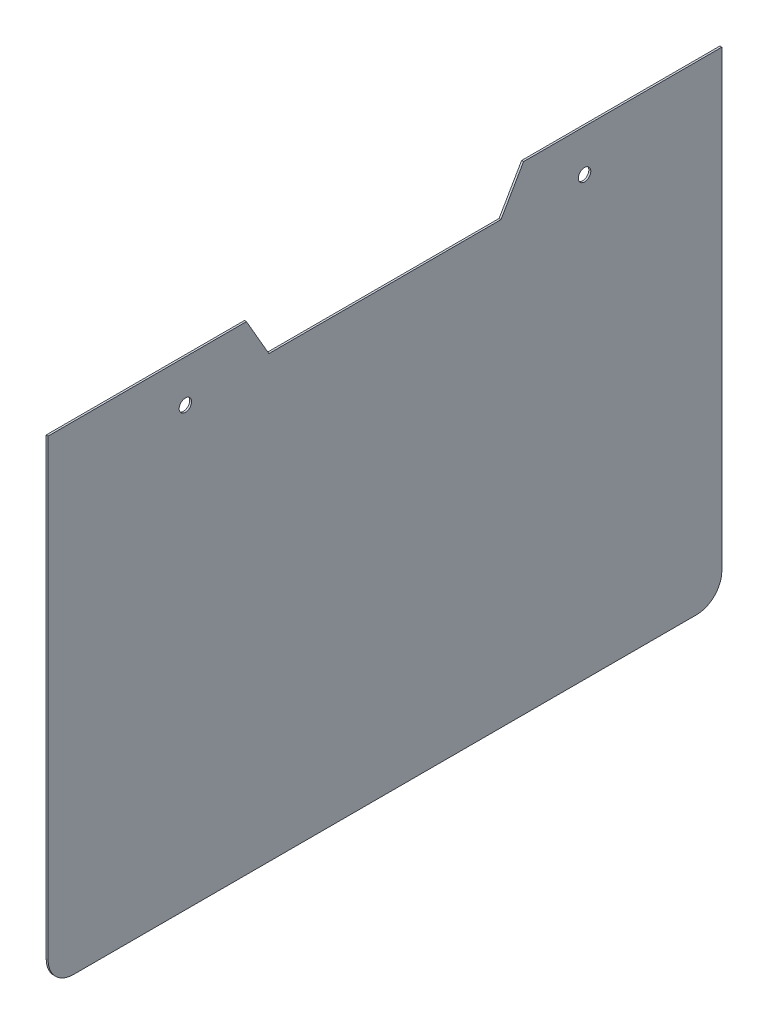
SolidWorks part; units mm, degrees
ref_plane "Front Plane" through (0, 0, 0) normal (0, 0, 1) x (1, 0, 0)
ref_plane "Top Plane" through (0, 0, 0) normal (0, 1, 0) x (1, 0, 0)
ref_plane "Right Plane" through (0, 0, 0) normal (1, 0, 0) x (0, 0, -1)
sketch "Sketch1" plane through (169.5336, 0, 0) normal (-1, 0, 0) x (0, 0, 1)
  line L0 (-82.9854, 164.2133) -> (-82.9854, 280.7133)
  line L1 (-82.9854, 280.7133) -> (-133.908, 280.7133)
  line L2 (-133.908, 280.7133) -> (-139.6815, 270.7133)
  line L3 (-139.6815, 270.7133) -> (-199.2892, 270.7133)
  line L4 (-199.2892, 270.7133) -> (-205.0627, 280.7133)
  line L5 (-205.0627, 280.7133) -> (-255.9854, 280.7133)
  line L6 (-255.9854, 280.7133) -> (-255.9854, 164.2133)
  line L7 (-249.4854, 157.7133) -> (-89.4854, 157.7133)
  line L8 (-81.9854, 164.2133) -> (-81.9854, 281.7133)
  line L9 (-81.9854, 281.7133) -> (-134.4854, 281.7133)
  line L10 (-134.4854, 281.7133) -> (-140.2589, 271.7133)
  line L11 (-140.2589, 271.7133) -> (-198.7119, 271.7133)
  line L12 (-198.7119, 271.7133) -> (-204.4854, 281.7133)
  line L13 (-204.4854, 281.7133) -> (-256.9854, 281.7133)
  line L14 (-256.9854, 281.7133) -> (-256.9854, 164.2133)
  line L15 (-249.4854, 156.7133) -> (-89.4854, 156.7133)
  line L16 (-81.9854, 164.2133) -> (-81.9854, 281.7133)
  line L17 (-81.9854, 281.7133) -> (-134.4854, 281.7133)
  line L18 (-134.4854, 281.7133) -> (-140.2589, 271.7133)
  line L19 (-140.2589, 271.7133) -> (-198.7119, 271.7133)
  line L20 (-198.7119, 271.7133) -> (-204.4854, 281.7133)
  line L21 (-204.4854, 281.7133) -> (-256.9854, 281.7133)
  line L22 (-256.9854, 281.7133) -> (-256.9854, 164.2133)
  line L23 (-249.4854, 156.7133) -> (-89.4854, 156.7133)
  arc A0 (-255.9854, 164.2133) -> (-249.4854, 157.7133) centre (-249.4854, 164.2133) ccw
  arc A1 (-89.4854, 157.7133) -> (-82.9854, 164.2133) centre (-89.4854, 164.2133) ccw
  arc A2 (-256.9854, 164.2133) -> (-249.4854, 156.7133) centre (-249.4854, 164.2133) ccw
  arc A3 (-89.4854, 156.7133) -> (-81.9854, 164.2133) centre (-89.4854, 164.2133) ccw
  arc A4 (-256.9854, 164.2133) -> (-249.4854, 156.7133) centre (-249.4854, 164.2133) ccw
  arc A5 (-89.4854, 156.7133) -> (-81.9854, 164.2133) centre (-89.4854, 164.2133) ccw
  dimension "D1" = 0
  dimension "D2" = 1
extrude "Boss-Extrude1" add sketch "Sketch1" along normal blind 0.5 contours L0 L1 L2 L3 L4 L5 L6 A0 L7 A1
sketch "Sketch2" plane through (169.0336, 0, 0) normal (-1, 0, 0) x (0, 0, 1)
  line L8 (-82.9854, 164.2133) -> (-82.9854, 280.7133)
  line L9 (-82.9854, 280.7133) -> (-133.908, 280.7133)
  line L10 (-133.908, 280.7133) -> (-139.6815, 270.7133)
  line L11 (-139.6815, 270.7133) -> (-199.2892, 270.7133)
  line L12 (-199.2892, 270.7133) -> (-205.0627, 280.7133)
  line L13 (-205.0627, 280.7133) -> (-255.9854, 280.7133)
  line L14 (-255.9854, 280.7133) -> (-255.9854, 164.2133)
  line L15 (-249.4854, 157.7133) -> (-89.4854, 157.7133)
  line L16 (-82.9854, 164.2133) -> (-82.9854, 280.7133)
  line L17 (-82.9854, 280.7133) -> (-133.908, 280.7133)
  line L18 (-133.908, 280.7133) -> (-139.6815, 270.7133)
  line L19 (-139.6815, 270.7133) -> (-199.2892, 270.7133)
  line L20 (-199.2892, 270.7133) -> (-205.0627, 280.7133)
  line L21 (-205.0627, 280.7133) -> (-255.9854, 280.7133)
  line L22 (-255.9854, 280.7133) -> (-255.9854, 164.2133)
  line L23 (-249.4854, 157.7133) -> (-89.4854, 157.7133)
  circle A0 centre (-118.2354, 269.9633) radius 1.25 construction
  circle A1 centre (-220.7354, 269.9633) radius 1.25 construction
  arc A2 (-89.4854, 157.7133) -> (-82.9854, 164.2133) centre (-89.4854, 164.2133) ccw
  arc A3 (-255.9854, 164.2133) -> (-249.4854, 157.7133) centre (-249.4854, 164.2133) ccw
  arc A4 (-89.4854, 157.7133) -> (-82.9854, 164.2133) centre (-89.4854, 164.2133) ccw
  arc A5 (-255.9854, 164.2133) -> (-249.4854, 157.7133) centre (-249.4854, 164.2133) ccw
  circle A6 centre (-118.2354, 269.9633) radius 1.25
  circle A7 centre (-220.7354, 269.9633) radius 1.25
  circle A8 centre (-220.7354, 269.9633) radius 1.6
  circle A9 centre (-118.2354, 269.9633) radius 1.6
  dimension "D2" = 3.2
  dimension "D3" = 3.2
  dimension "D1" = 0
extrude "Cut-Extrude2" cut sketch "Sketch2" against normal up to next contours A6 | A7 | A9 A6 | A8 A7 region at (169.0336, 269.9633, -118.2354) region at (169.0336, 269.9633, -220.7354) region at (169.0336, 269.9633, -222.2901) region at (169.0336, 269.9633, -119.7901)
sketch "Sketch4" plane through (169.0336, 0, -163.2571) normal (-1, 0, 0) x (0, 0, 1)
  line L0 (-13.9255, 240.4892) -> (-13.9255, 240.4522)
  line L1 (-6.3225, 222.7198) -> (-6.3055, 222.7103)
  line L2 (-6.3055, 222.7103) -> (-6.2886, 222.7198)
  line L3 (1.3145, 240.4543) -> (1.3145, 240.4913)
  line L4 (1.3145, 240.4913) -> (-13.9255, 240.4892)
  line L5 (-6.2283, 270.7133) -> (-6.2283, 157.7133) construction
  line L6 (0.7451, 239.8542) -> (0.7451, 239.8796)
  line L7 (0.7451, 239.8796) -> (-13.3752, 239.8775)
  line L8 (-13.3752, 239.8775) -> (-13.3752, 239.8521)
  line L9 (-6.3119, 223.3992) -> (-6.3003, 223.3929)
  line L10 (-6.3003, 223.3929) -> (-6.2886, 223.3992)
  line L11 (-10.4362, 235.5606) -> (-6.2367, 236.8708)
  line L12 (-6.2367, 236.8708) -> (-2.0203, 235.5606)
  line L13 (-2.0203, 235.5606) -> (-10.4362, 235.5606)
  line L14 (-4.0788, 236.2876) -> (-4.0788, 237.3714)
  line L15 (-4.0788, 237.3714) -> (-8.3534, 237.3714)
  line L16 (-8.3534, 237.3714) -> (-8.3534, 236.2982)
  line L17 (-8.3534, 236.2982) -> (-6.2367, 236.9586)
  line L18 (-6.2367, 236.9586) -> (-4.0788, 236.2876)
  line L19 (-6.7638, 238.2011) -> (-5.697, 238.2011)
  line L20 (-5.7182, 238.164) -> (-6.7289, 238.164)
  line L21 (-7.8528, 237.4094) -> (-4.5942, 237.4095)
  line L22 (-8.7672, 229.6339) -> (-8.7672, 228.3882)
  line L23 (-8.927, 228.256) -> (-9.1302, 228.2475)
  line L24 (-9.1302, 228.2475) -> (-9.1302, 228.1427)
  line L25 (-8.0602, 228.1427) -> (-8.0602, 228.2475)
  line L26 (-8.0602, 228.2475) -> (-8.2359, 228.256)
  line L27 (-8.3957, 228.3882) -> (-8.3957, 229.2942)
  line L28 (-8.3671, 230.0075) -> (-8.4021, 230.0371)
  line L29 (-9.2032, 229.5556) -> (-8.8095, 229.7376)
  line L30 (-7.2125, 229.001) -> (-7.0411, 228.9248)
  line L31 (-6.9257, 229.2571) -> (-7.0495, 229.309)
  line L32 (-5.5912, 229.6339) -> (-5.5912, 228.3882)
  line L33 (-5.751, 228.256) -> (-5.9542, 228.2475)
  line L34 (-5.9542, 228.2475) -> (-5.9542, 228.1427)
  line L35 (-4.8831, 228.1427) -> (-4.8831, 228.2475)
  line L36 (-4.8831, 228.2475) -> (-5.0588, 228.256)
  line L37 (-5.2186, 228.3882) -> (-5.2186, 229.2942)
  line L38 (-5.1911, 230.0075) -> (-5.225, 230.0371)
  line L39 (-6.0261, 229.5556) -> (-5.6335, 229.7376)
  line L40 (-4.1074, 229.6339) -> (-4.1074, 228.3882)
  line L41 (-4.2672, 228.256) -> (-4.4693, 228.2475)
  line L42 (-4.4693, 228.2475) -> (-4.4693, 228.1427)
  line L43 (-3.3994, 228.1427) -> (-3.3994, 228.2475)
  line L44 (-3.3994, 228.2475) -> (-3.5751, 228.256)
  line L45 (-3.7359, 228.3882) -> (-3.7359, 229.2942)
  line L46 (-3.7074, 230.0075) -> (-3.7413, 230.0371)
  line L47 (-4.5424, 229.5556) -> (-4.1497, 229.7376)
  line L48 (-5.697, 232.8152) -> (-5.7192, 232.8152)
  line L49 (-5.7192, 232.8152) -> (-5.7192, 232.5961)
  line L50 (-5.7192, 232.5961) -> (-5.4716, 232.5866)
  line L51 (-5.2472, 232.448) -> (-5.2472, 231.8955)
  line L52 (-4.9519, 234.0492) -> (-4.9308, 233.6873)
  line L53 (-4.9308, 233.6873) -> (-4.9297, 233.6682)
  line L54 (-4.9297, 233.6682) -> (-4.7233, 233.6682)
  line L55 (-4.7233, 233.6682) -> (-4.7138, 233.754)
  line L56 (-4.6228, 234.3424) -> (-4.6197, 234.3509)
  line L57 (-4.6197, 234.3509) -> (-4.6535, 234.4112)
  line L58 (-4.6535, 234.4112) -> (-4.6599, 234.4144)
  line L59 (-4.6048, 231.7696) -> (-4.5911, 231.7749)
  line L60 (-4.5911, 231.7749) -> (-4.5911, 232.4924)
  line L61 (-4.3879, 232.6258) -> (-4.3709, 232.629)
  line L62 (-4.3709, 232.629) -> (-4.3709, 232.8152)
  line L63 (-4.3709, 232.8152) -> (-4.3921, 232.8142)
  line L64 (-7.9513, 234.3435) -> (-7.7724, 234.3583)
  line L65 (-7.7724, 234.3583) -> (-7.7724, 234.5594)
  line L66 (-7.7724, 234.5594) -> (-7.7947, 234.5594)
  line L67 (-8.7885, 234.5583) -> (-8.8033, 234.5583)
  line L68 (-8.8033, 234.5583) -> (-8.8085, 234.5446)
  line L69 (-9.0191, 234.0588) -> (-9.7885, 232.4713)
  line L70 (-9.7885, 232.4713) -> (-10.4489, 233.8514)
  line L71 (-10.7728, 234.5446) -> (-10.7792, 234.5583)
  line L72 (-10.7792, 234.5583) -> (-10.7929, 234.5583)
  line L73 (-11.8259, 234.5583) -> (-11.8481, 234.5583)
  line L74 (-11.8481, 234.5583) -> (-11.8481, 234.3572)
  line L75 (-11.8481, 234.3572) -> (-11.6693, 234.3424)
  line L76 (-11.4819, 233.9424) -> (-11.4819, 232.1856)
  line L77 (-11.6693, 231.7855) -> (-11.8481, 231.7707)
  line L78 (-11.8481, 231.7707) -> (-11.8481, 231.5696)
  line L79 (-11.8481, 231.5696) -> (-11.8259, 231.5696)
  line L80 (-10.8405, 231.5696) -> (-10.8183, 231.5696)
  line L81 (-10.8183, 231.5696) -> (-10.8183, 231.7707)
  line L82 (-10.8183, 231.7707) -> (-10.9982, 231.7855)
  line L83 (-11.1855, 232.1856) -> (-11.1855, 233.8884)
  line L84 (-11.1855, 233.8884) -> (-10.2362, 231.9104)
  line L85 (-10.2362, 231.9104) -> (-10.2193, 231.8744)
  line L86 (-10.0827, 231.5548) -> (-10.0775, 231.541)
  line L87 (-10.0775, 231.541) -> (-9.9007, 231.541)
  line L88 (-9.9007, 231.541) -> (-9.8954, 231.5548)
  line L89 (-9.6383, 232.1231) -> (-8.7916, 233.8852)
  line L90 (-8.7916, 233.8852) -> (-8.7916, 232.1876)
  line L91 (-8.9779, 231.8014) -> (-9.1567, 231.7866)
  line L92 (-9.1567, 231.7866) -> (-9.1567, 231.5728)
  line L93 (-9.1567, 231.5728) -> (-9.0191, 231.5759)
  line L94 (-7.9142, 231.5759) -> (-7.7734, 231.5728)
  line L95 (-7.7734, 231.5728) -> (-7.7734, 231.7866)
  line L96 (-7.7734, 231.7866) -> (-7.9533, 231.8014)
  line L97 (-8.1407, 232.1887) -> (-8.1407, 233.9456)
  line L98 (-0.9557, 234.3308) -> (-0.7747, 234.3456)
  line L99 (-0.7747, 234.3456) -> (-0.7747, 234.5583)
  line L100 (-0.7747, 234.5583) -> (-0.7969, 234.5583)
  line L101 (-2.1484, 234.5583) -> (-2.1707, 234.5583)
  line L102 (-2.1707, 234.5583) -> (-2.1707, 234.3456)
  line L103 (-2.1707, 234.3456) -> (-1.9907, 234.3308)
  line L104 (-1.8023, 233.9424) -> (-1.8023, 233.282)
  line L105 (-2.1325, 233.2746) -> (-2.7686, 233.2746)
  line L106 (-3.0988, 233.282) -> (-3.0988, 233.9424)
  line L107 (-2.9093, 234.3308) -> (-2.7294, 234.3456)
  line L108 (-2.7294, 234.3456) -> (-2.7294, 234.5583)
  line L109 (-2.7294, 234.5583) -> (-2.7517, 234.5583)
  line L110 (-4.1021, 234.5583) -> (-4.1243, 234.5583)
  line L111 (-4.1243, 234.5583) -> (-4.1243, 234.3456)
  line L112 (-4.1243, 234.3456) -> (-3.9434, 234.3308)
  line L113 (-3.7561, 233.9434) -> (-3.7561, 232.1866)
  line L114 (-3.9445, 231.7971) -> (-4.1254, 231.7833)
  line L115 (-4.1254, 231.7833) -> (-4.1254, 231.5685)
  line L116 (-4.1254, 231.5685) -> (-4.0281, 231.5716)
  line L117 (-2.8311, 231.5716) -> (-2.7305, 231.5685)
  line L118 (-2.7305, 231.5685) -> (-2.7305, 231.7833)
  line L119 (-2.7305, 231.7833) -> (-2.9104, 231.7971)
  line L120 (-3.0999, 232.1866) -> (-3.0999, 232.9846)
  line L121 (-2.7697, 232.992) -> (-2.1336, 232.992)
  line L122 (-1.8034, 232.9846) -> (-1.8034, 232.1866)
  line L123 (-1.9928, 231.7971) -> (-2.1727, 231.7833)
  line L124 (-2.1727, 231.7833) -> (-2.1727, 231.5685)
  line L125 (-2.1727, 231.5685) -> (-2.0743, 231.5716)
  line L126 (-0.8763, 231.5716) -> (-0.7768, 231.5685)
  line L127 (-0.7768, 231.5685) -> (-0.7768, 231.7833)
  line L128 (-0.7768, 231.7833) -> (-0.9577, 231.7971)
  line L129 (-1.1461, 232.1855) -> (-1.1461, 233.9424)
  line L131 (-86.2283, 157.7133) -> (73.7717, 157.7133) construction
  line L133 (-6.3055, 240.4903) -> (-6.3055, 222.7103) construction
  line L134 (23.5756, 270.7133) -> (-36.0321, 270.7133) construction
  spline S0 degree 3 poles (-13.9255, 240.4522) (-13.9255, 232.1824) (-13.9255, 226.7203) (-6.3225, 222.7198) knots 0.125 0.125 0.125 0.125 0.25 0.25 0.25 0.25
  spline S1 degree 3 poles (-6.2886, 222.7198) (1.3145, 226.7034) (1.3145, 232.1739) (1.3145, 240.4543) knots 0.5 0.5 0.5 0.5 0.625 0.625 0.625 0.625
  spline S4 degree 3 poles (-13.3752, 239.8521) (-13.3752, 239.6256) (-13.3752, 239.3991) (-13.3763, 239.1737) knots 0.25 0.25 0.25 0.25 0.333333 0.333333 0.333333 0.333333
  spline S5 degree 3 poles (-13.3763, 239.1737) (-13.3815, 236.0336) (-13.3858, 233.0682) (-12.5042, 230.3493) knots 0.333333 0.333333 0.333333 0.333333 0.416667 0.416667 0.416667 0.416667
  spline S6 degree 3 poles (-12.5042, 230.3493) (-12.0301, 228.8867) (-11.3432, 227.64) (-10.4045, 226.5372) knots 0.416667 0.416667 0.416667 0.416667 0.5 0.5 0.5 0.5
  spline S7 degree 3 poles (-10.4045, 226.5372) (-9.3535, 225.3021) (-8.0147, 224.2756) (-6.3119, 223.3992) knots 0.5 0.5 0.5 0.5 0.583333 0.583333 0.583333 0.583333
  spline S8 degree 3 poles (-6.2886, 223.3992) (0.7588, 227.06) (0.7525, 232.9888) (0.7451, 239.2636) knots 0.75 0.75 0.75 0.75 0.833333 0.833333 0.833333 0.833333
  spline S9 degree 3 poles (0.7451, 239.2636) (0.7451, 239.4605) (0.7451, 239.6574) (0.7451, 239.8542) knots 0.833333 0.833333 0.833333 0.833333 1 1 1 1
  spline S10 degree 3 poles (-5.697, 238.2011) (-5.6917, 238.5673) (-5.9859, 238.8467) (-6.2378, 239.07) knots 0.25 0.25 0.25 0.25 0.5 0.5 0.5 0.5
  spline S11 degree 3 poles (-6.2378, 239.07) (-6.4865, 238.8424) (-6.7638, 238.5779) (-6.7638, 238.2011) knots 0.5 0.5 0.5 0.5 1 1 1 1
  spline S12 degree 3 poles (-6.7289, 238.164) (-7.239, 238.0497) (-7.6539, 237.7714) (-7.8528, 237.4094) knots 0.2 0.2 0.2 0.2 0.4 0.4 0.4 0.4
  spline S13 degree 3 poles (-4.5942, 237.4095) (-4.7932, 237.7714) (-5.2081, 238.0508) (-5.7182, 238.164) knots 0.6 0.6 0.6 0.6 1 1 1 1
  spline S14 degree 3 poles (-8.8095, 229.7376) (-8.7651, 229.7577) (-8.7672, 229.6932) (-8.7672, 229.6339) knots 0 0 0 0 0.058824 0.058824 0.058824 0.058824
  spline S15 degree 3 poles (-8.7672, 228.3882) (-8.7672, 228.293) (-8.8371, 228.2612) (-8.927, 228.256) knots 0.117647 0.117647 0.117647 0.117647 0.176471 0.176471 0.176471 0.176471
  spline S16 degree 3 poles (-9.1302, 228.1427) (-8.8011, 228.1459) (-8.6794, 228.1512) (-8.5587, 228.1512) knots 0.294118 0.294118 0.294118 0.294118 0.352941 0.352941 0.352941 0.352941
  spline S17 degree 3 poles (-8.5587, 228.1512) (-8.4349, 228.1512) (-8.3163, 228.1459) (-8.0602, 228.1427) knots 0.352941 0.352941 0.352941 0.352941 0.411765 0.411765 0.411765 0.411765
  spline S18 degree 3 poles (-8.2359, 228.256) (-8.3248, 228.2612) (-8.3957, 228.292) (-8.3957, 228.3882) knots 0.529412 0.529412 0.529412 0.529412 0.588235 0.588235 0.588235 0.588235
  spline S19 degree 3 poles (-8.3957, 229.2942) (-8.3957, 229.6307) (-8.3767, 229.872) (-8.3671, 230.0075) knots 0.647059 0.647059 0.647059 0.647059 0.705882 0.705882 0.705882 0.705882
  spline S20 degree 3 poles (-8.4021, 230.0371) (-8.6444, 229.9408) (-9.0371, 229.8011) (-9.2424, 229.7524) knots 0.764706 0.764706 0.764706 0.764706 0.823529 0.823529 0.823529 0.823529
  spline S21 degree 3 poles (-9.2424, 229.7524) (-9.2466, 229.6932) (-9.2339, 229.6307) (-9.2032, 229.5556) knots 0.823529 0.823529 0.823529 0.823529 0.882353 0.882353 0.882353 0.882353
  spline S22 degree 3 poles (-7.0411, 228.9248) (-6.8813, 228.8539) (-6.7479, 228.766) (-6.7479, 228.5692) knots 0 0 0 0 0.166667 0.166667 0.166667 0.166667
  spline S23 degree 3 poles (-6.7479, 228.5692) (-6.7479, 228.3978) (-6.8718, 228.2485) (-7.0496, 228.2485) knots 0.166667 0.166667 0.166667 0.166667 0.333333 0.333333 0.333333 0.333333
  spline S24 degree 3 poles (-7.0496, 228.2485) (-7.2602, 228.2485) (-7.4062, 228.4178) (-7.4062, 228.6232) knots 0.333333 0.333333 0.333333 0.333333 0.5 0.5 0.5 0.5
  spline S25 degree 3 poles (-7.4062, 228.6232) (-7.4062, 228.7957) (-7.3385, 228.8941) (-7.2125, 229.001) knots 0.5 0.5 0.5 0.5 0.666667 0.666667 0.666667 0.666667
  spline S26 degree 3 poles (-7.0495, 229.309) (-7.1818, 229.3661) (-7.3194, 229.4423) (-7.3194, 229.6116) knots 0 0 0 0 0.166667 0.166667 0.166667 0.166667
  spline S27 degree 3 poles (-7.3194, 229.6116) (-7.3194, 229.7714) (-7.2041, 229.8614) (-7.0495, 229.8614) knots 0.166667 0.166667 0.166667 0.166667 0.333333 0.333333 0.333333 0.333333
  spline S28 degree 3 poles (-7.0495, 229.8614) (-6.8665, 229.8614) (-6.7595, 229.7323) (-6.7595, 229.5556) knots 0.333333 0.333333 0.333333 0.333333 0.5 0.5 0.5 0.5
  spline S29 degree 3 poles (-6.7595, 229.5556) (-6.7595, 229.4423) (-6.8167, 229.3439) (-6.9257, 229.2571) knots 0.5 0.5 0.5 0.5 0.666667 0.666667 0.666667 0.666667
  spline S30 degree 3 poles (-7.0136, 230.0075) (-7.3956, 230.0075) (-7.6094, 229.7948) (-7.6094, 229.4847) knots 0 0 0 0 0.111111 0.111111 0.111111 0.111111
  spline S31 degree 3 poles (-7.6094, 229.4847) (-7.6094, 229.2825) (-7.5036, 229.1439) (-7.329, 229.0518) knots 0.111111 0.111111 0.111111 0.111111 0.222222 0.222222 0.222222 0.222222
  spline S32 degree 3 poles (-7.329, 229.0518) (-7.5089, 228.9725) (-7.6581, 228.801) (-7.6581, 228.5957) knots 0.222222 0.222222 0.222222 0.222222 0.333333 0.333333 0.333333 0.333333
  spline S33 degree 3 poles (-7.6581, 228.5957) (-7.6581, 228.3544) (-7.4867, 228.1036) (-7.0919, 228.1036) knots 0.333333 0.333333 0.333333 0.333333 0.444444 0.444444 0.444444 0.444444
  spline S34 degree 3 poles (-7.0919, 228.1036) (-6.7321, 228.1036) (-6.4389, 228.3565) (-6.4389, 228.7248) knots 0.444444 0.444444 0.444444 0.444444 0.555556 0.555556 0.555556 0.555556
  spline S35 degree 3 poles (-6.4389, 228.7248) (-6.4389, 229.0116) (-6.6369, 229.1545) (-6.7882, 229.2095) knots 0.555556 0.555556 0.555556 0.555556 0.666667 0.666667 0.666667 0.666667
  spline S36 degree 3 poles (-6.7882, 229.2095) (-6.6305, 229.3101) (-6.5236, 229.435) (-6.5236, 229.5948) knots 0.666667 0.666667 0.666667 0.666667 0.777778 0.777778 0.777778 0.777778
  spline S37 degree 3 poles (-6.5236, 229.5948) (-6.5235, 229.8815) (-6.7532, 230.0075) (-7.0136, 230.0075) knots 0.777778 0.777778 0.777778 0.777778 1 1 1 1
  spline S38 degree 3 poles (-5.6335, 229.7376) (-5.5891, 229.7577) (-5.5912, 229.6932) (-5.5912, 229.6339) knots 0 0 0 0 0.058824 0.058824 0.058824 0.058824
  spline S39 degree 3 poles (-5.5912, 228.3882) (-5.5912, 228.293) (-5.661, 228.2612) (-5.751, 228.256) knots 0.117647 0.117647 0.117647 0.117647 0.176471 0.176471 0.176471 0.176471
  spline S40 degree 3 poles (-5.9542, 228.1427) (-5.625, 228.1459) (-5.5033, 228.1512) (-5.3827, 228.1512) knots 0.294118 0.294118 0.294118 0.294118 0.352941 0.352941 0.352941 0.352941
  spline S41 degree 3 poles (-5.3827, 228.1512) (-5.2588, 228.1512) (-5.1403, 228.1459) (-4.8831, 228.1427) knots 0.352941 0.352941 0.352941 0.352941 0.411765 0.411765 0.411765 0.411765
  spline S42 degree 3 poles (-5.0588, 228.256) (-5.1488, 228.2612) (-5.2186, 228.292) (-5.2186, 228.3882) knots 0.529412 0.529412 0.529412 0.529412 0.588235 0.588235 0.588235 0.588235
  spline S43 degree 3 poles (-5.2186, 229.2942) (-5.2186, 229.6307) (-5.1996, 229.872) (-5.1911, 230.0075) knots 0.647059 0.647059 0.647059 0.647059 0.705882 0.705882 0.705882 0.705882
  spline S44 degree 3 poles (-5.225, 230.0371) (-5.4663, 229.9408) (-5.86, 229.8011) (-6.0663, 229.7524) knots 0.764706 0.764706 0.764706 0.764706 0.823529 0.823529 0.823529 0.823529
  spline S45 degree 3 poles (-6.0663, 229.7524) (-6.0685, 229.6932) (-6.0579, 229.6307) (-6.0261, 229.5556) knots 0.823529 0.823529 0.823529 0.823529 0.882353 0.882353 0.882353 0.882353
  spline S46 degree 3 poles (-4.1497, 229.7376) (-4.1053, 229.7577) (-4.1074, 229.6932) (-4.1074, 229.6339) knots 0 0 0 0 0.058824 0.058824 0.058824 0.058824
  spline S47 degree 3 poles (-4.1074, 228.3882) (-4.1074, 228.293) (-4.1772, 228.2612) (-4.2672, 228.256) knots 0.117647 0.117647 0.117647 0.117647 0.176471 0.176471 0.176471 0.176471
  spline S48 degree 3 poles (-4.4693, 228.1427) (-4.1402, 228.1459) (-4.0185, 228.1512) (-3.8989, 228.1512) knots 0.294118 0.294118 0.294118 0.294118 0.352941 0.352941 0.352941 0.352941
  spline S49 degree 3 poles (-3.8989, 228.1512) (-3.7751, 228.1512) (-3.6565, 228.1459) (-3.3994, 228.1427) knots 0.352941 0.352941 0.352941 0.352941 0.411765 0.411765 0.411765 0.411765
  spline S50 degree 3 poles (-3.5751, 228.256) (-3.665, 228.2612) (-3.7359, 228.292) (-3.7359, 228.3882) knots 0.529412 0.529412 0.529412 0.529412 0.588235 0.588235 0.588235 0.588235
  spline S51 degree 3 poles (-3.7359, 229.2942) (-3.7359, 229.6307) (-3.7169, 229.872) (-3.7074, 230.0075) knots 0.647059 0.647059 0.647059 0.647059 0.705882 0.705882 0.705882 0.705882
  spline S52 degree 3 poles (-3.7413, 230.0371) (-3.9826, 229.9408) (-4.3763, 229.8011) (-4.5826, 229.7524) knots 0.764706 0.764706 0.764706 0.764706 0.823529 0.823529 0.823529 0.823529
  spline S53 degree 3 poles (-4.5826, 229.7524) (-4.5858, 229.6932) (-4.5741, 229.6307) (-4.5424, 229.5556) knots 0.823529 0.823529 0.823529 0.823529 0.882353 0.882353 0.882353 0.882353
  spline S54 degree 3 poles (-4.3921, 232.8142) (-4.4524, 232.8131) (-4.5159, 232.811) (-4.5815, 232.8099) knots 0 0 0 0 0.03125 0.03125 0.03125 0.03125
  spline S55 degree 3 poles (-4.5815, 232.8099) (-4.7445, 232.8057) (-4.9149, 232.8014) (-5.0651, 232.8014) knots 0.03125 0.03125 0.03125 0.03125 0.0625 0.0625 0.0625 0.0625
  spline S56 degree 3 poles (-5.0651, 232.8014) (-5.1943, 232.8014) (-5.3265, 232.8046) (-5.4546, 232.8088) knots 0.0625 0.0625 0.0625 0.0625 0.09375 0.09375 0.09375 0.09375
  spline S57 degree 3 poles (-5.4546, 232.8088) (-5.5351, 232.811) (-5.6165, 232.8131) (-5.697, 232.8152) knots 0.09375 0.09375 0.09375 0.09375 0.125 0.125 0.125 0.125
  spline S58 degree 3 poles (-5.4716, 232.5866) (-5.3255, 232.5813) (-5.2472, 232.557) (-5.2472, 232.448) knots 0.21875 0.21875 0.21875 0.21875 0.25 0.25 0.25 0.25
  spline S59 degree 3 poles (-5.2472, 231.8955) (-5.4324, 231.8267) (-5.5997, 231.7939) (-5.7721, 231.7939) knots 0.28125 0.28125 0.28125 0.28125 0.3125 0.3125 0.3125 0.3125
  spline S60 degree 3 poles (-5.7721, 231.7939) (-6.6103, 231.7939) (-6.9077, 232.5337) (-6.9077, 233.1676) knots 0.3125 0.3125 0.3125 0.3125 0.34375 0.34375 0.34375 0.34375
  spline S61 degree 3 poles (-6.9077, 233.1676) (-6.9077, 233.8873) (-6.4971, 234.3339) (-5.8357, 234.3339) knots 0.34375 0.34375 0.34375 0.34375 0.375 0.375 0.375 0.375
  spline S62 degree 3 poles (-5.8357, 234.3339) (-5.4494, 234.3339) (-5.1043, 234.2228) (-4.9519, 234.0492) knots 0.375 0.375 0.375 0.375 0.40625 0.40625 0.40625 0.40625
  spline S63 degree 3 poles (-4.7138, 233.754) (-4.6916, 233.9445) (-4.6599, 234.2059) (-4.6228, 234.3424) knots 0.53125 0.53125 0.53125 0.53125 0.5625 0.5625 0.5625 0.5625
  spline S64 degree 3 poles (-4.6599, 234.4144) (-5.097, 234.5943) (-5.5076, 234.6186) (-5.8516, 234.6186) knots 0.65625 0.65625 0.65625 0.65625 0.6875 0.6875 0.6875 0.6875
  spline S65 degree 3 poles (-5.8516, 234.6186) (-6.7194, 234.6186) (-7.5957, 234.1529) (-7.5957, 233.1126) knots 0.6875 0.6875 0.6875 0.6875 0.71875 0.71875 0.71875 0.71875
  spline S66 degree 3 poles (-7.5957, 233.1126) (-7.5957, 232.1252) (-6.9343, 231.5114) (-5.8695, 231.5114) knots 0.71875 0.71875 0.71875 0.71875 0.75 0.75 0.75 0.75
  spline S67 degree 3 poles (-5.8695, 231.5114) (-5.4674, 231.5114) (-5.0536, 231.596) (-4.6048, 231.7696) knots 0.75 0.75 0.75 0.75 0.78125 0.78125 0.78125 0.78125
  spline S68 degree 3 poles (-4.5911, 232.4924) (-4.5911, 232.5803) (-4.5392, 232.5951) (-4.3879, 232.6258) knots 0.84375 0.84375 0.84375 0.84375 0.875 0.875 0.875 0.875
  spline S69 degree 3 poles (-8.1111, 234.2821) (-8.0952, 234.3138) (-8.0634, 234.3339) (-7.9513, 234.3435) knots 0 0 0 0 0.015152 0.015152 0.015152 0.015152
  spline S70 degree 3 poles (-7.7947, 234.5594) (-7.8846, 234.5572) (-7.964, 234.5551) (-8.036, 234.552) knots 0.060606 0.060606 0.060606 0.060606 0.075758 0.075758 0.075758 0.075758
  spline S71 degree 3 poles (-8.036, 234.552) (-8.1344, 234.5488) (-8.2201, 234.5456) (-8.2942, 234.5456) knots 0.075758 0.075758 0.075758 0.075758 0.090909 0.090909 0.090909 0.090909
  spline S72 degree 3 poles (-8.2942, 234.5456) (-8.3673, 234.5456) (-8.454, 234.5488) (-8.5535, 234.552) knots 0.090909 0.090909 0.090909 0.090909 0.106061 0.106061 0.106061 0.106061
  spline S73 degree 3 poles (-8.5535, 234.552) (-8.6244, 234.5541) (-8.7017, 234.5572) (-8.7885, 234.5583) knots 0.106061 0.106061 0.106061 0.106061 0.121212 0.121212 0.121212 0.121212
  spline S74 degree 3 poles (-8.8085, 234.5446) (-8.8276, 234.5012) (-8.8467, 234.4556) (-8.8657, 234.408) knots 0.151515 0.151515 0.151515 0.151515 0.166667 0.166667 0.166667 0.166667
  spline S75 degree 3 poles (-8.8657, 234.408) (-8.9144, 234.2916) (-8.9641, 234.171) (-9.0191, 234.0588) knots 0.166667 0.166667 0.166667 0.166667 0.181818 0.181818 0.181818 0.181818
  spline S76 degree 3 poles (-10.4489, 233.8514) (-10.4796, 233.917) (-10.5167, 233.9964) (-10.5569, 234.08) knots 0.212121 0.212121 0.212121 0.212121 0.227273 0.227273 0.227273 0.227273
  spline S77 degree 3 poles (-10.5569, 234.08) (-10.6341, 234.243) (-10.7209, 234.4282) (-10.7728, 234.5446) knots 0.227273 0.227273 0.227273 0.227273 0.242424 0.242424 0.242424 0.242424
  spline S78 degree 3 poles (-10.7929, 234.5583) (-10.8406, 234.5573) (-10.8882, 234.5552) (-10.9369, 234.5541) knots 0.272727 0.272727 0.272727 0.272727 0.287879 0.287879 0.287879 0.287879
  spline S79 degree 3 poles (-10.9369, 234.5541) (-11.1792, 234.5456) (-11.4353, 234.5446) (-11.6809, 234.5541) knots 0.287879 0.287879 0.287879 0.287879 0.30303 0.30303 0.30303 0.30303
  spline S80 degree 3 poles (-11.6809, 234.5541) (-11.7295, 234.5551) (-11.7772, 234.5572) (-11.8259, 234.5583) knots 0.30303 0.30303 0.30303 0.30303 0.318182 0.318182 0.318182 0.318182
  spline S81 degree 3 poles (-11.6693, 234.3424) (-11.5581, 234.334) (-11.5264, 234.3128) (-11.5095, 234.2821) knots 0.363636 0.363636 0.363636 0.363636 0.378788 0.378788 0.378788 0.378788
  spline S82 degree 3 poles (-11.5095, 234.2821) (-11.4872, 234.2334) (-11.4819, 234.1212) (-11.4819, 233.9424) knots 0.378788 0.378788 0.378788 0.378788 0.393939 0.393939 0.393939 0.393939
  spline S83 degree 3 poles (-11.4819, 232.1856) (-11.4819, 232.0109) (-11.4862, 231.8934) (-11.5095, 231.848) knots 0.409091 0.409091 0.409091 0.409091 0.424242 0.424242 0.424242 0.424242
  spline S84 degree 3 poles (-11.5095, 231.848) (-11.5264, 231.8152) (-11.5581, 231.794) (-11.6693, 231.7855) knots 0.424242 0.424242 0.424242 0.424242 0.439394 0.439394 0.439394 0.439394
  spline S85 degree 3 poles (-11.8259, 231.5696) (-11.774, 231.5707) (-11.7211, 231.5728) (-11.6682, 231.5749) knots 0.484848 0.484848 0.484848 0.484848 0.5 0.5 0.5 0.5
  spline S86 degree 3 poles (-11.6682, 231.5749) (-11.5571, 231.5792) (-11.4427, 231.5834) (-11.3316, 231.5834) knots 0.5 0.5 0.5 0.5 0.515152 0.515152 0.515152 0.515152
  spline S87 degree 3 poles (-11.3316, 231.5834) (-11.2205, 231.5834) (-11.1083, 231.5792) (-10.9993, 231.5749) knots 0.515152 0.515152 0.515152 0.515152 0.530303 0.530303 0.530303 0.530303
  spline S88 degree 3 poles (-10.9993, 231.5749) (-10.9464, 231.5728) (-10.8935, 231.5707) (-10.8405, 231.5696) knots 0.530303 0.530303 0.530303 0.530303 0.545455 0.545455 0.545455 0.545455
  spline S89 degree 3 poles (-10.9982, 231.7855) (-11.1083, 231.794) (-11.1411, 231.8152) (-11.158, 231.8469) knots 0.590909 0.590909 0.590909 0.590909 0.606061 0.606061 0.606061 0.606061
  spline S90 degree 3 poles (-11.158, 231.8469) (-11.1813, 231.8935) (-11.1855, 232.011) (-11.1855, 232.1856) knots 0.606061 0.606061 0.606061 0.606061 0.621212 0.621212 0.621212 0.621212
  spline S91 degree 3 poles (-10.2193, 231.8744) (-10.1685, 231.7654) (-10.1208, 231.6627) (-10.0827, 231.5548) knots 0.666667 0.666667 0.666667 0.666667 0.681818 0.681818 0.681818 0.681818
  spline S92 degree 3 poles (-9.8954, 231.5548) (-9.8383, 231.6987) (-9.7536, 231.885) (-9.6383, 232.1231) knots 0.727273 0.727273 0.727273 0.727273 0.742424 0.742424 0.742424 0.742424
  spline S93 degree 3 poles (-8.7916, 232.1876) (-8.7916, 232.013) (-8.7958, 231.8955) (-8.8191, 231.85) knots 0.772727 0.772727 0.772727 0.772727 0.787879 0.787879 0.787879 0.787879
  spline S94 degree 3 poles (-8.8191, 231.85) (-8.8329, 231.8225) (-8.8794, 231.8077) (-8.9779, 231.8014) knots 0.787879 0.787879 0.787879 0.787879 0.80303 0.80303 0.80303 0.80303
  spline S95 degree 3 poles (-9.0191, 231.5759) (-8.8625, 231.5802) (-8.6688, 231.5854) (-8.4635, 231.5854) knots 0.848485 0.848485 0.848485 0.848485 0.863636 0.863636 0.863636 0.863636
  spline S96 degree 3 poles (-8.4635, 231.5854) (-8.2634, 231.5854) (-8.0697, 231.5802) (-7.9142, 231.5759) knots 0.863636 0.863636 0.863636 0.863636 0.878788 0.878788 0.878788 0.878788
  spline S97 degree 3 poles (-7.9533, 231.8014) (-8.0518, 231.8088) (-8.0983, 231.8236) (-8.1131, 231.85) knots 0.924242 0.924242 0.924242 0.924242 0.939394 0.939394 0.939394 0.939394
  spline S98 degree 3 poles (-8.1131, 231.85) (-8.1364, 231.8966) (-8.1407, 232.0141) (-8.1407, 232.1887) knots 0.939394 0.939394 0.939394 0.939394 0.954545 0.954545 0.954545 0.954545
  spline S99 degree 3 poles (-8.1407, 233.9456) (-8.1386, 234.1212) (-8.1343, 234.2345) (-8.1111, 234.2821) knots 0.969697 0.969697 0.969697 0.969697 1 1 1 1
  spline S100 degree 3 poles (-1.1155, 234.2821) (-1.1017, 234.3085) (-1.0541, 234.3234) (-0.9557, 234.3308) knots 0 0 0 0 0.015385 0.015385 0.015385 0.015385
  spline S101 degree 3 poles (-0.7969, 234.5583) (-0.8456, 234.5572) (-0.8985, 234.5562) (-0.9557, 234.5551) knots 0.061538 0.061538 0.061538 0.061538 0.076923 0.076923 0.076923 0.076923
  spline S102 degree 3 poles (-0.9557, 234.5551) (-1.1091, 234.5509) (-1.2849, 234.5466) (-1.4711, 234.5466) knots 0.076923 0.076923 0.076923 0.076923 0.092308 0.092308 0.092308 0.092308
  spline S103 degree 3 poles (-1.4711, 234.5466) (-1.6605, 234.5466) (-1.8352, 234.5509) (-1.9907, 234.5551) knots 0.092308 0.092308 0.092308 0.092308 0.107692 0.107692 0.107692 0.107692
  spline S104 degree 3 poles (-1.9907, 234.5551) (-2.0479, 234.5562) (-2.1008, 234.5583) (-2.1484, 234.5583) knots 0.107692 0.107692 0.107692 0.107692 0.123077 0.123077 0.123077 0.123077
  spline S105 degree 3 poles (-1.9907, 234.3308) (-1.8913, 234.3234) (-1.8436, 234.3085) (-1.8299, 234.2821) knots 0.169231 0.169231 0.169231 0.169231 0.184615 0.184615 0.184615 0.184615
  spline S106 degree 3 poles (-1.8299, 234.2821) (-1.8045, 234.2313) (-1.8023, 234.0926) (-1.8023, 233.9424) knots 0.184615 0.184615 0.184615 0.184615 0.2 0.2 0.2 0.2
  spline S107 degree 3 poles (-1.8023, 233.282) (-1.8648, 233.2788) (-1.9495, 233.2746) (-2.1325, 233.2746) knots 0.215385 0.215385 0.215385 0.215385 0.230769 0.230769 0.230769 0.230769
  spline S108 degree 3 poles (-2.7686, 233.2746) (-2.9517, 233.2746) (-3.0363, 233.2788) (-3.0988, 233.282) knots 0.246154 0.246154 0.246154 0.246154 0.261538 0.261538 0.261538 0.261538
  spline S109 degree 3 poles (-3.0988, 233.9424) (-3.0988, 234.099) (-3.0967, 234.2324) (-3.0713, 234.2821) knots 0.276923 0.276923 0.276923 0.276923 0.292308 0.292308 0.292308 0.292308
  spline S110 degree 3 poles (-3.0713, 234.2821) (-3.0575, 234.3085) (-3.0099, 234.3234) (-2.9093, 234.3308) knots 0.292308 0.292308 0.292308 0.292308 0.307692 0.307692 0.307692 0.307692
  spline S111 degree 3 poles (-2.7517, 234.5583) (-2.8003, 234.5572) (-2.8543, 234.5562) (-2.9115, 234.5551) knots 0.353846 0.353846 0.353846 0.353846 0.369231 0.369231 0.369231 0.369231
  spline S112 degree 3 poles (-2.9115, 234.5551) (-3.0649, 234.5509) (-3.2395, 234.5466) (-3.4237, 234.5466) knots 0.369231 0.369231 0.369231 0.369231 0.384615 0.384615 0.384615 0.384615
  spline S113 degree 3 poles (-3.4237, 234.5466) (-3.6131, 234.5466) (-3.7899, 234.5509) (-3.9444, 234.5551) knots 0.384615 0.384615 0.384615 0.384615 0.4 0.4 0.4 0.4
  spline S114 degree 3 poles (-3.9444, 234.5551) (-4.0005, 234.5562) (-4.0534, 234.5583) (-4.1021, 234.5583) knots 0.4 0.4 0.4 0.4 0.415385 0.415385 0.415385 0.415385
  spline S115 degree 3 poles (-3.9434, 234.3308) (-3.8449, 234.3234) (-3.7963, 234.3085) (-3.7836, 234.2821) knots 0.461538 0.461538 0.461538 0.461538 0.476923 0.476923 0.476923 0.476923
  spline S116 degree 3 poles (-3.7836, 234.2821) (-3.7582, 234.2334) (-3.7561, 234.099) (-3.7561, 233.9434) knots 0.476923 0.476923 0.476923 0.476923 0.492308 0.492308 0.492308 0.492308
  spline S117 degree 3 poles (-3.7561, 232.1866) (-3.7561, 232.0299) (-3.7582, 231.8976) (-3.7836, 231.8468) knots 0.507692 0.507692 0.507692 0.507692 0.523077 0.523077 0.523077 0.523077
  spline S118 degree 3 poles (-3.7836, 231.8468) (-3.7973, 231.8193) (-3.8429, 231.8056) (-3.9445, 231.7971) knots 0.523077 0.523077 0.523077 0.523077 0.538462 0.538462 0.538462 0.538462
  spline S119 degree 3 poles (-4.0281, 231.5716) (-3.8598, 231.5759) (-3.6513, 231.5822) (-3.4259, 231.5822) knots 0.584615 0.584615 0.584615 0.584615 0.6 0.6 0.6 0.6
  spline S120 degree 3 poles (-3.4259, 231.5822) (-3.2068, 231.5822) (-2.9983, 231.5759) (-2.8311, 231.5716) knots 0.6 0.6 0.6 0.6 0.615385 0.615385 0.615385 0.615385
  spline S121 degree 3 poles (-2.9104, 231.7971) (-3.012, 231.8056) (-3.0586, 231.8193) (-3.0723, 231.8468) knots 0.661538 0.661538 0.661538 0.661538 0.676923 0.676923 0.676923 0.676923
  spline S122 degree 3 poles (-3.0723, 231.8468) (-3.0977, 231.8966) (-3.0999, 232.0299) (-3.0999, 232.1866) knots 0.676923 0.676923 0.676923 0.676923 0.692308 0.692308 0.692308 0.692308
  spline S123 degree 3 poles (-3.0999, 232.9846) (-3.0374, 232.9888) (-2.9527, 232.992) (-2.7697, 232.992) knots 0.707692 0.707692 0.707692 0.707692 0.723077 0.723077 0.723077 0.723077
  spline S124 degree 3 poles (-2.1336, 232.992) (-1.9505, 232.992) (-1.8658, 232.9888) (-1.8034, 232.9846) knots 0.738462 0.738462 0.738462 0.738462 0.753846 0.753846 0.753846 0.753846
  spline S125 degree 3 poles (-1.8034, 232.1866) (-1.8034, 232.0363) (-1.8055, 231.8987) (-1.8309, 231.8468) knots 0.769231 0.769231 0.769231 0.769231 0.784615 0.784615 0.784615 0.784615
  spline S126 degree 3 poles (-1.8309, 231.8468) (-1.8447, 231.8193) (-1.8912, 231.8056) (-1.9928, 231.7971) knots 0.784615 0.784615 0.784615 0.784615 0.8 0.8 0.8 0.8
  spline S127 degree 3 poles (-2.0743, 231.5716) (-1.9071, 231.5769) (-1.6975, 231.5822) (-1.4732, 231.5822) knots 0.846154 0.846154 0.846154 0.846154 0.861538 0.861538 0.861538 0.861538
  spline S128 degree 3 poles (-1.4732, 231.5822) (-1.252, 231.5822) (-1.0435, 231.5759) (-0.8763, 231.5716) knots 0.861538 0.861538 0.861538 0.861538 0.876923 0.876923 0.876923 0.876923
  spline S129 degree 3 poles (-0.9577, 231.7971) (-1.0583, 231.8056) (-1.1049, 231.8193) (-1.1175, 231.8468) knots 0.923077 0.923077 0.923077 0.923077 0.938462 0.938462 0.938462 0.938462
  spline S130 degree 3 poles (-1.1175, 231.8468) (-1.144, 231.8966) (-1.1461, 232.0299) (-1.1461, 232.1855) knots 0.938462 0.938462 0.938462 0.938462 0.953846 0.953846 0.953846 0.953846
  spline S131 degree 3 poles (-1.1461, 233.9424) (-1.1441, 234.099) (-1.1419, 234.2324) (-1.1155, 234.2821) knots 0.969231 0.969231 0.969231 0.969231 1 1 1 1
  point P4 (-6.2283, 270.7133)
  point P274 (-6.3055, 231.6003)
extrude "Cut-Extrude3" cut sketch "Sketch4" against normal blind 0.25 contours L2 S1 L3 L4 L0 S0 L1 S9 S8 L10 L9 S7 S6 S5 S4 L8 L7 L6 | L17 L18 L14 L15 L16 | L21 S13 L20 S12 | L97 S99 S69 L64 L65 L66 S70 S71 S72 S73 L67 L68 S74 S75 L69 L70 S76 S77 L71 L72 S78 S79 S80 L73 L74 L75 S81 S82 L76 S83 S84 L77 L78 L79 S85 S86 S87 S88 L80 L81 L82 S89 S90 L83 L84 L85 S91 L86 L87 L88 S92 | L60 S68 L61 L62 L63 S54 S55 S56 S57 L48 L49 L50 S58 L51 S59 S60 S61 S62 L52 L53 L54 L55 S63 L56 L57 L58 S64 S65 S66 S67 L59 | L129 S131 S100 L98 L99 L100 S101 S102 S103 S104 L101 L102 L103 S105 S106 L104 S107 L105 S108 L106 S109 S110 L107 L108 L109 S111 S112 S113 S114 L110 L111 L112 S115 S116 L113 S117 S118 L114 L115 L116 S119 S120 L117 L118 L119 S121 S122 L120 S123 L121 S124 | S20 S21 L29 S14 L22 S15 L23 L24 S16 S17 L25 L26 S18 L27 S19 L28 | S36 S37 S30 S31 S32 S33 S34 S35 S28 S29 L31 S26 S27 S24 S25 L30 S22 S23 | S44 S45 L39 S38 L32 S39 L33 L34 S40 S41 L35 L36 S42 L37 S43 L38 | S52 S53 L47 S46 L40 S47 L41 L42 S48 S49 L43 L44 S50 L45 S51 L46 | S10 S11 L19 region at (169.0336, 240.2561, -169.5626) region at (169.0336, 236.9738, -169.4651) region at (169.0336, 237.7349, -169.4804) region at (169.0336, 229.0471, -171.8782) region at (169.0336, 229.0467, -168.7015) region at (169.0336, 229.0467, -167.2182) region at (169.0336, 232.7673, -168.8341) region at (169.0336, 234.3794, -171.3091) region at (169.0336, 233.0698, -165.7077) region at (169.0336, 229.0545, -170.308)
ref_point "Point1"
